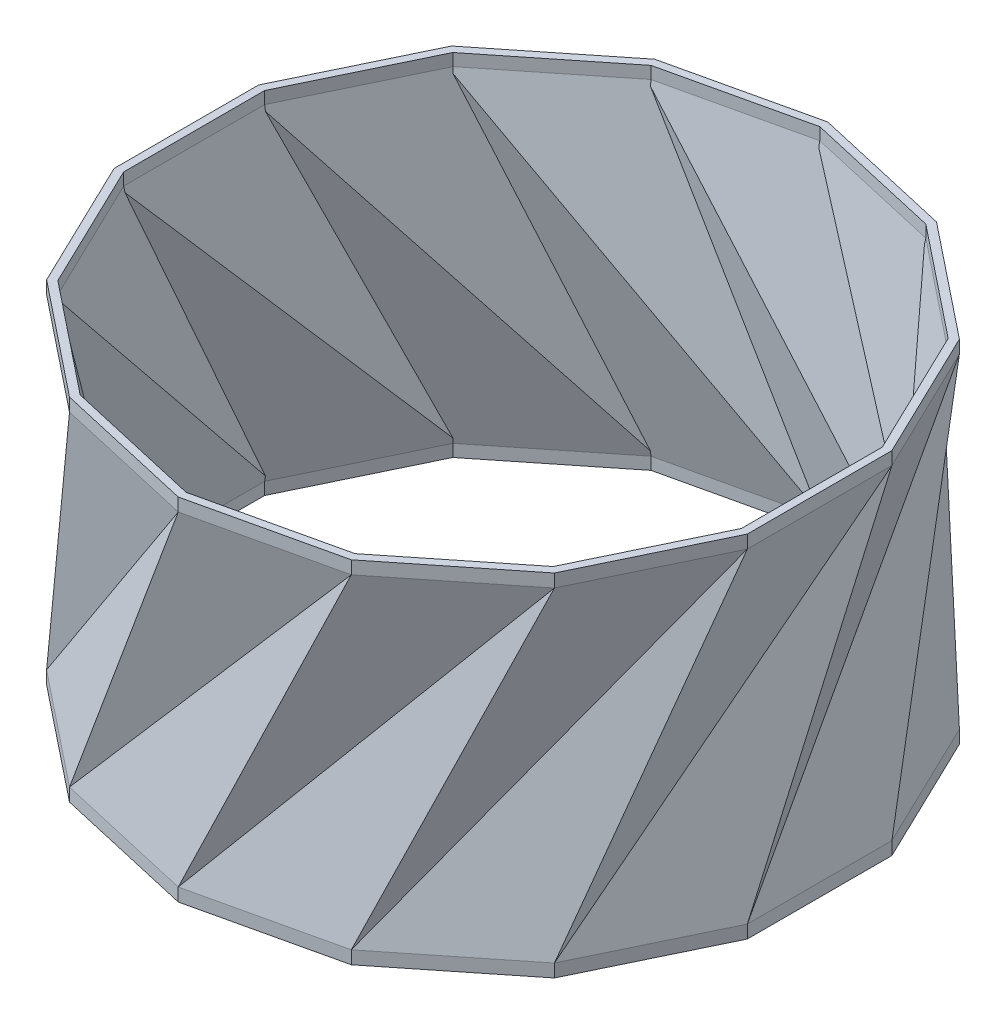
SolidWorks part; units mm, degrees
ref_plane "정면" through (0, 0, 0) normal (0, 0, 1) x (1, 0, 0)
ref_plane "윗면" through (0, 0, 0) normal (0, 1, 0) x (1, 0, 0)
ref_plane "우측면" through (0, 0, 0) normal (1, 0, 0) x (0, 0, -1)
sketch "스케치1" plane through (0, 0, 0) normal (0, 1, 0) x (1, 0, 0)
  line L0 (-55, 0) -> (55, 0) construction
  line L1 (19.5458, -15.5872) -> (24.3732, -5.563)
  line L2 (24.3732, -5.563) -> (24.3732, 5.563)
  line L3 (24.3732, 5.563) -> (19.5458, 15.5872)
  line L4 (19.5458, 15.5872) -> (10.8471, 22.5242)
  line L5 (10.8471, 22.5242) -> (0, 25)
  line L6 (0, 25) -> (-10.8471, 22.5242)
  line L7 (-10.8471, 22.5242) -> (-19.5458, 15.5872)
  line L8 (-19.5458, 15.5872) -> (-24.3732, 5.563)
  line L9 (-24.3732, 5.563) -> (-24.3732, -5.563)
  line L10 (-24.3732, -5.563) -> (-19.5458, -15.5872)
  line L11 (-19.5458, -15.5872) -> (-10.8471, -22.5242)
  line L12 (-10.8471, -22.5242) -> (0, -25)
  line L13 (0, -25) -> (10.8471, -22.5242)
  line L14 (10.8471, -22.5242) -> (19.5458, -15.5872)
  circle A0 centre (0, 0) radius 25 construction
  dimension "D1" = 50
extrude "보스-돌출1" add sketch "스케치1" along normal blind 25
ref_plane "평면1" through (-5.2286, 4.5372, 22.908) normal (-0.2185, 0.1896, 0.9572) x (0.9758, 0.0424, 0.2143)
sketch "스케치2" plane through (-5.2286, 4.5372, 22.908) normal (-0.2185, 0.1896, 0.9572) x (0.9758, 0.0424, 0.2143)
  line L0 (-5.7576, -4.3762) -> (16.4737, 20.1474)
  line L1 (16.4737, 20.1474) -> (5.358, -4.8572)
sketch "스케치3" plane through (-5.4235, 0, 23.7621) normal (-0.2225, 0, 0.9749) x (0.9749, 0, 0.2225)
  line L0 (-5.563, 0) -> (5.563, 25)
ref_plane "평면2" through (-10.8471, 0, 22.5242) normal (0.6554, 0.7553, 0) x (0.7553, -0.6554, 0)
sketch "스케치4" plane through (-10.8471, 0, 22.5242) normal (0.6554, 0.7553, 0) x (0.7553, -0.6554, 0)
  line L0 (0, 0) -> (8.1926, -2.4758) construction
  line L1 (0, 0) -> (-8.1926, -2.4758) construction
  line L2 (0, 0) -> (8.1926, -2.4758)
  line L3 (0, 0) -> (-8.1926, -2.4758)
  line L4 (-8.1926, -2.4758) -> (8.1926, -2.4758)
extrude "컷-돌출1" cut sketch "스케치4" along normal up to vertex (33.1004 mm away) up to point (10.8471, 25, 22.5242)
pattern_circular "원형 패턴1" count 14 over 360 about axis through (0, 25, 0) along (0, 1, 0) of "컷-돌출1"
sketch "스케치5" plane through (0, 25, 0) normal (0, 1, 0) x (1, 0, 0)
  line L14 (10.8471, -22.5242) -> (19.5458, -15.5872)
  line L15 (19.5458, -15.5872) -> (24.3732, -5.563)
  line L16 (24.3732, -5.563) -> (24.3732, 5.563)
  line L17 (24.3732, 5.563) -> (19.5458, 15.5872)
  line L18 (19.5458, 15.5872) -> (10.8471, 22.5242)
  line L19 (10.8471, 22.5242) -> (0, 25)
  line L20 (0, 25) -> (-10.8471, 22.5242)
  line L21 (-10.8471, 22.5242) -> (-19.5458, 15.5872)
  line L22 (-19.5458, 15.5872) -> (-24.3732, 5.563)
  line L23 (-24.3732, 5.563) -> (-24.3732, -5.563)
  line L24 (-24.3732, -5.563) -> (-19.5458, -15.5872)
  line L25 (-19.5458, -15.5872) -> (-10.8471, -22.5242)
  line L26 (-10.8471, -22.5242) -> (0, -25)
  line L27 (0, -25) -> (10.8471, -22.5242)
  line L28 (10.8471, -22.5242) -> (19.5458, -15.5872)
  line L29 (19.5458, -15.5872) -> (24.3732, -5.563)
  line L30 (24.3732, -5.563) -> (24.3732, 5.563)
  line L31 (24.3732, 5.563) -> (19.5458, 15.5872)
  line L32 (19.5458, 15.5872) -> (10.8471, 22.5242)
  line L33 (10.8471, 22.5242) -> (0, 25)
  line L34 (0, 25) -> (-10.8471, 22.5242)
  line L35 (-10.8471, 22.5242) -> (-19.5458, 15.5872)
  line L36 (-19.5458, 15.5872) -> (-24.3732, 5.563)
  line L37 (-24.3732, 5.563) -> (-24.3732, -5.563)
  line L38 (-24.3732, -5.563) -> (-19.5458, -15.5872)
  line L39 (-19.5458, -15.5872) -> (-10.8471, -22.5242)
  line L40 (-10.8471, -22.5242) -> (0, -25)
  line L41 (0, -25) -> (10.8471, -22.5242)
  dimension "D1" = 0
extrude "보스-돌출2" add sketch "스케치5" along normal blind 1
sketch "스케치6" plane through (0, 0, 0) normal (0, -1, 0) x (1, 0, 0)
  line L14 (19.5458, 15.5872) -> (10.8471, 22.5242)
  line L15 (10.8471, 22.5242) -> (0, 25)
  line L16 (0, 25) -> (-10.8471, 22.5242)
  line L17 (-10.8471, 22.5242) -> (-19.5458, 15.5872)
  line L18 (-19.5458, 15.5872) -> (-24.3732, 5.563)
  line L19 (-24.3732, 5.563) -> (-24.3732, -5.563)
  line L20 (-24.3732, -5.563) -> (-19.5458, -15.5872)
  line L21 (-19.5458, -15.5872) -> (-10.8471, -22.5242)
  line L22 (-10.8471, -22.5242) -> (0, -25)
  line L23 (0, -25) -> (10.8471, -22.5242)
  line L24 (10.8471, -22.5242) -> (19.5458, -15.5872)
  line L25 (19.5458, -15.5872) -> (24.3732, -5.563)
  line L26 (24.3732, -5.563) -> (24.3732, 5.563)
  line L27 (24.3732, 5.563) -> (19.5458, 15.5872)
  line L28 (19.5458, 15.5872) -> (10.8471, 22.5242)
  line L29 (10.8471, 22.5242) -> (0, 25)
  line L30 (0, 25) -> (-10.8471, 22.5242)
  line L31 (-10.8471, 22.5242) -> (-19.5458, 15.5872)
  line L32 (-19.5458, 15.5872) -> (-24.3732, 5.563)
  line L33 (-24.3732, 5.563) -> (-24.3732, -5.563)
  line L34 (-24.3732, -5.563) -> (-19.5458, -15.5872)
  line L35 (-19.5458, -15.5872) -> (-10.8471, -22.5242)
  line L36 (-10.8471, -22.5242) -> (0, -25)
  line L37 (0, -25) -> (10.8471, -22.5242)
  line L38 (10.8471, -22.5242) -> (19.5458, -15.5872)
  line L39 (19.5458, -15.5872) -> (24.3732, -5.563)
  line L40 (24.3732, -5.563) -> (24.3732, 5.563)
  line L41 (24.3732, 5.563) -> (19.5458, 15.5872)
  dimension "D1" = 0
extrude "보스-돌출3" add sketch "스케치6" along normal blind 1
shell "쉘1" thickness 0.6 removed face at (0, 26, 0) removed face at (0, -1, 0)
